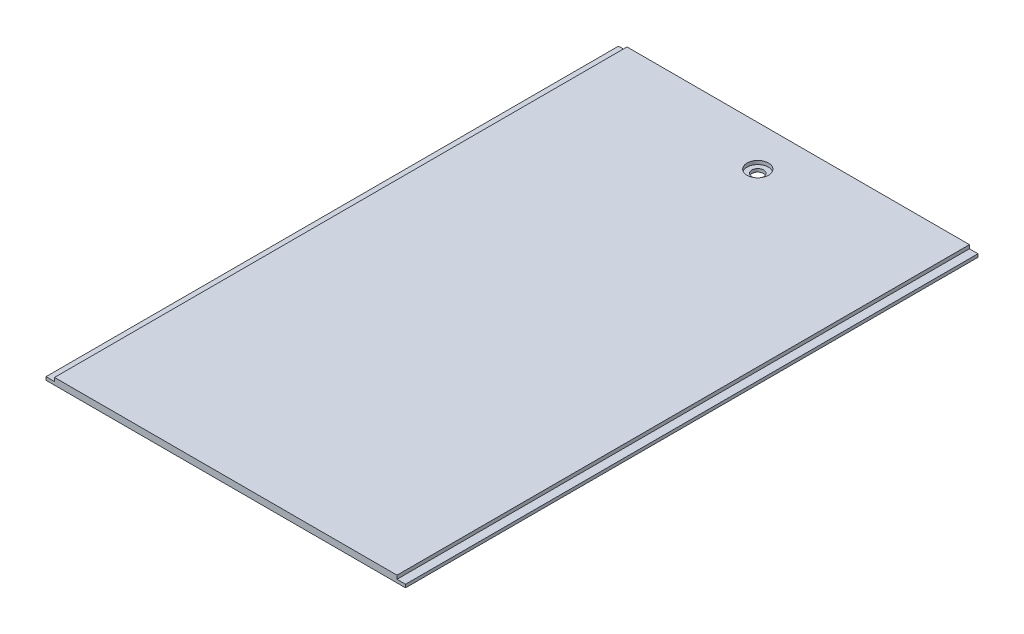
SolidWorks part; units mm, degrees
material "PLA"
ref_plane "Спереди" through (0, 0, 0) normal (0, 0, 1) x (1, 0, 0)
ref_plane "Сверху" through (0, 0, 0) normal (0, 1, 0) x (1, 0, 0)
ref_plane "Справа" through (0, 0, 0) normal (1, 0, 0) x (0, 0, -1)
sketch "Эскиз1" plane through (0, 0, 0) normal (0, 1, 0) x (1, 0, 0)
  line L1 (38.075, 63.65) -> (-38.075, 63.65)
  line L2 (38.075, 63.65) -> (38.075, -63.65)
  line L3 (38.075, -63.65) -> (-38.075, -63.65)
  line L4 (-38.075, 63.65) -> (-38.075, -63.65)
  line L5 (38.075, 63.65) -> (-38.075, -63.65) construction
  line L6 (38.075, -63.65) -> (-38.075, 63.65) construction
  point P0 (0, 0)
  dimension "D1" = 76.15
  dimension "D2" = 127.3
extrude "Бобышка-Вытянуть1" add sketch "Эскиз1" along normal blind 1.5
sketch "Эскиз2" plane through (0, 0, 63.65) normal (0, 0, 1) x (1, 0, 0)
  line L0 (0, 0) -> (0, -50000) construction
  line L1 (-38.075, 0) -> (-39.975, 0)
  line L2 (-38.075, 0) -> (-38.075, 0.7)
  line L3 (-38.075, 0.7) -> (-39.975, 0.7)
  line L4 (-39.975, 0) -> (-39.975, 0.7)
  line L5 (38.075, 0.7) -> (39.975, 0.7)
  line L6 (39.975, 0) -> (39.975, 0.7)
  line L7 (38.075, 0) -> (39.975, 0)
  line L8 (38.075, 0) -> (38.075, 0.7)
  dimension "D1" = 0.7
  dimension "D2" = 1.9
extrude "Бобышка-Вытянуть2" add sketch "Эскиз2" against normal up to surface (127.3 mm away) up to face at (0, 0.75, -63.65)
sketch "Эскиз3" plane through (0, 1.5, 0) normal (0, 1, 0) x (1, 0, 0)
  line L0 (0, 0) -> (0, 50000) construction
  line L1 (38.075, 63.65) -> (-38.075, 63.65) construction
  circle A0 centre (0, 54.65) radius 1.3
  dimension "D1" = 2.6
  dimension "D2" = 9
extrude "Вырез-Вытянуть1" cut sketch "Эскиз3" against normal through all
sketch "Эскиз5" plane through (0, 1.5, 0) normal (0, 1, 0) x (1, 0, 0)
  circle A0 centre (0, 54.65) radius 2.375
  dimension "D1" = 4.75
extrude "Вырез-Вытянуть2" cut sketch "Эскиз5" against normal blind 0.8
